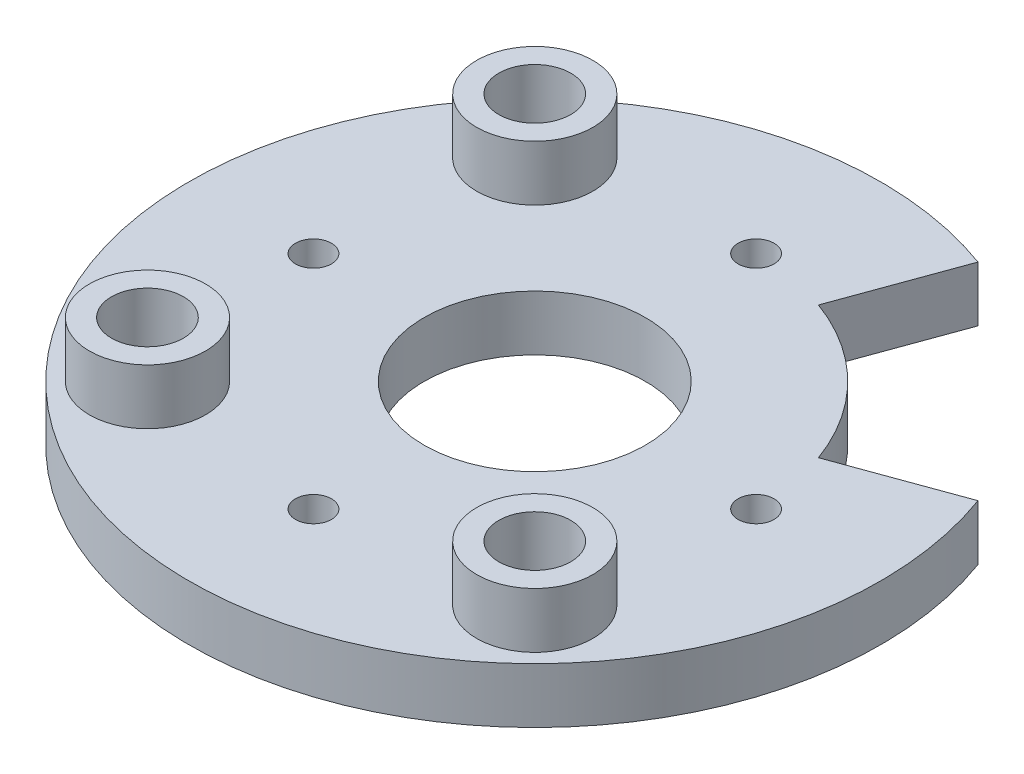
SolidWorks part; units mm, degrees
ref_plane "前视基准面" through (0, 0, 0) normal (0, 0, 1) x (1, 0, 0)
ref_plane "上视基准面" through (0, 0, 0) normal (0, 1, 0) x (1, 0, 0)
ref_plane "右视基准面" through (0, 0, 0) normal (1, 0, 0) x (0, 0, -1)
sketch "草图1" plane through (0, 0, 0) normal (0, 1, 0) x (1, 0, 0)
  line L0 (0, 0) -> (8, 0) construction
  line L1 (0, 0) -> (0, 8) construction
  circle A0 centre (0, 0) radius 8 construction
  circle A1 centre (8, 0) radius 0.65
  circle A2 centre (0, -8) radius 0.65
  circle A3 centre (-8, 0) radius 0.65
  circle A4 centre (0, 8) radius 0.65
  circle A5 centre (0, 0) radius 4
  circle A6 centre (0, 0) radius 12.5
  dimension "D1" = 16
  dimension "D2" = 1.3
  dimension "D4" = 8
  dimension "D5" = 25
  dimension "D3" = 4
extrude "凸台-拉伸1" add sketch "草图1" along normal blind 2 contours A6 A1 A2 A3 A4 A5 region at (-12.1464, 0, 0)
sketch "草图5" plane through (0, 2, 0) normal (0, 1, 0) x (1, 0, 0)
  line L0 (0, 0) -> (0, 12.5) construction
  line L2 (0, 0) -> (8.8388, -8.8388) construction
  circle A0 centre (0, 0) radius 12.5 construction
  circle A1 centre (7, -7) radius 1.3
  circle A2 centre (7, -7) radius 2.1
  circle A3 centre (-7, -7) radius 2.1
  circle A4 centre (-7, -7) radius 1.3
  circle A5 centre (-7, 7) radius 2.1
  circle A6 centre (-7, 7) radius 1.3
  circle A7 centre (7, 7) radius 2.1
  circle A8 centre (7, 7) radius 1.3
  dimension "D2" = 2.6
  dimension "D3" = 4.2
  dimension "D1" = 135
  dimension "D5" = 14
  dimension "D4" = 4
extrude "切除-拉伸3" cut sketch "草图5" against normal up to surface (2 mm away) contours A4 | A1 | A8 | A6 region at (7, 2, 7) region at (-7, 2, 7) region at (-7, 2, -7) region at (7, 2, -7) up to face at (8, 0, 0.65)
extrude "凸台-拉伸3" add sketch "草图5<3>" along normal blind 2 contours A5 A6 | A2 A1 | A3 A4 region at (4.9594, 2, 7) region at (-9.0406, 2, 7) region at (-9.0406, 2, -7)
sketch "草图5<3>" plane through (0, 2, 0) normal (0, 1, 0) x (1, 0, 0) same geometry as "草图5"
sketch "草图6" plane through (0, 2, 0) normal (0, 1, 0) x (1, 0, 0)
  line L0 (0, 0) -> (11.7462, 4.2753)
  line L1 (0, 0) -> (4.2753, 11.7462)
  line L2 (0, 0) -> (2.9782, 0) construction
  circle A0 centre (0, 0) radius 4 construction
  circle A1 centre (0, 0) radius 12.5
  circle A2 centre (0, 0) radius 12.5
  circle A3 centre (0, 0) radius 4
  circle A4 centre (0, 0) radius 8
  circle M13 centre (0, 0) radius 4
  circle M14 centre (0, 0) radius 12.5
  dimension "D2" = 20
  dimension "D3" = 70
  dimension "D1" = 0
extrude "切除-拉伸4" cut sketch "草图6" against normal up to surface (2 mm away) contours L1 L0 M13 M14 region at (7.1328, 2, -7.1328) up to face at (-7, 0, -5.7)
